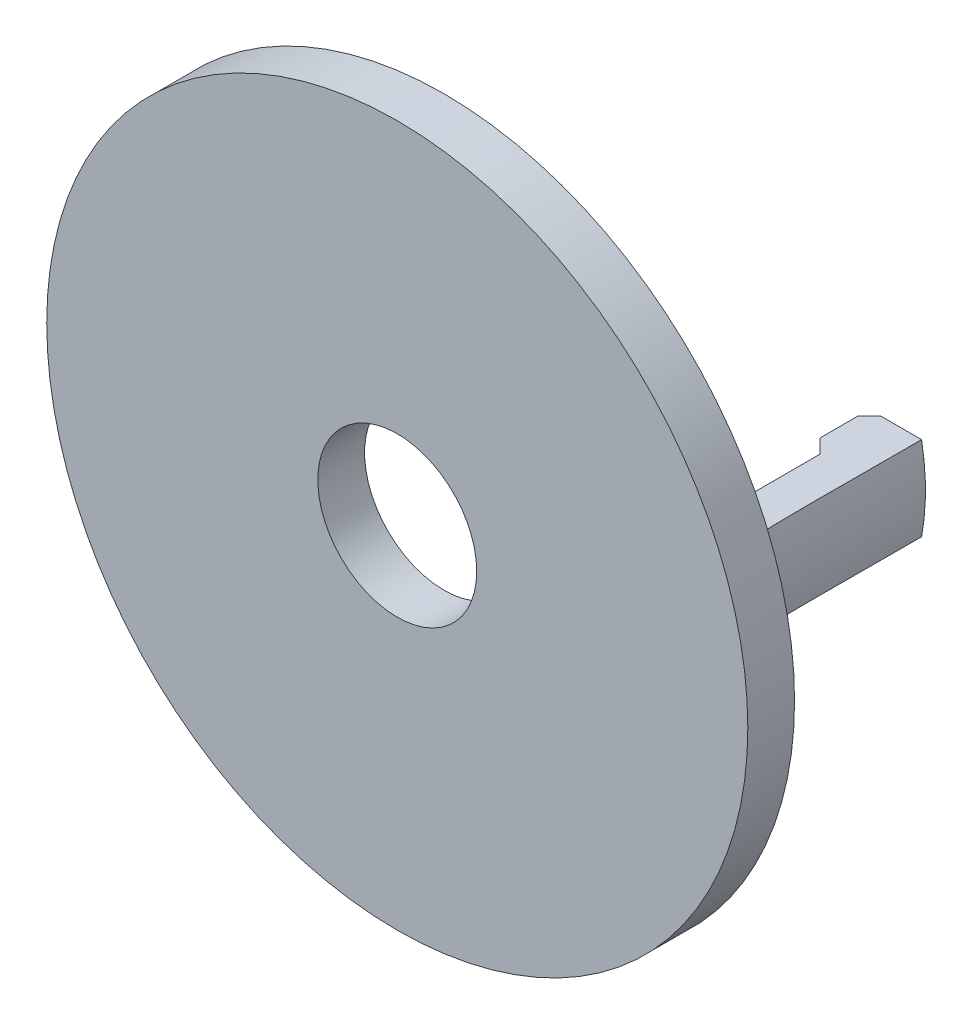
SolidWorks part; units mm, degrees
ref_plane "Front" through (0, 0, 0) normal (0, 0, 1) x (1, 0, 0)
ref_plane "Top" through (0, 0, 0) normal (0, 1, 0) x (1, 0, 0)
ref_plane "Right" through (0, 0, 0) normal (1, 0, 0) x (0, 0, -1)
sketch "Sketch1" plane through (0, 0, 0) normal (0, 0, 1) x (1, 0, 0)
  circle A0 centre (0, 0) radius 26.5
  circle A1 centre (0, 0) radius 37.5
  circle A2 centre (-2, 0) radius 26.5
  dimension "D1" = 53
  dimension "D2" = 75
  dimension "D3" = 2
sketch "Sketch4" plane through (0, 0, 0) normal (0, 0, 1) x (1, 0, 0)
  circle A0 centre (0, 0) radius 37.5
  dimension "D1" = 75
extrude "Boss-Extrude2" add sketch "Sketch4" along normal blind 5
sketch "Sketch5" plane through (0, 0, 5) normal (0, 0, 1) x (1, 0, 0)
  circle A0 centre (0, 0) radius 8.5
  dimension "D1" = 17
extrude "Cut-Extrude1" cut sketch "Sketch5" against normal through all
sketch "Sketch6" plane through (0, 0, 0) normal (0, 1, 0) x (1, 0, 0)
  line L0 (20, 0) -> (26.5, 0) construction
  line L1 (26.5, 0) -> (26.5, 27) construction
  line L2 (17.7071, 0) -> (26.5, 0)
  line L3 (26.5, 27) -> (20, 27) construction
  line L4 (20, 27) -> (18.5, 25.5) construction
  line L5 (18.5, 21) -> (20, 19.5) construction
  line L6 (20, 19.5) -> (20, 0) construction
  line L7 (20.5, 19.7071) -> (20.5, 2.7929)
  line L8 (20, 3) -> (17, 0) construction
  line L9 (20.5, 19.7071) -> (19, 21.2071)
  line L10 (18.5, 25.5) -> (18.5, 21) construction
  line L11 (19, 21.2071) -> (19, 25.2929)
  line L12 (26.5, 0) -> (26.5, 26.5)
  line L13 (17, 0) -> (20, 0) construction
  line L14 (20.5, 2.7929) -> (17.7071, 0)
  line L15 (19, 25.2929) -> (20.2071, 26.5)
  line L16 (20.2071, 26.5) -> (26.5, 26.5)
  line L17 (25, 26.5113) -> (25, 41.0721) construction
  line L18 (25, 12.4795) -> (25, 18.7128) construction
  spline S0 degree 3 poles (25, 26.5) (25, 22.4782) (24.9901, 20.5563) (25.0119, 14.9305) (24.7749, 4.9839) (26.5, 0) knots 0 0 0 0 0.446605 0.546605 1 1 1 1
  dimension "D1" = 135
  dimension "D2" = 6.5
  dimension "D3" = 8
  dimension "D4" = 27
  dimension "D5" = 7.5
  dimension "D6" = 0.5
  dimension "D7" = 0.5
  dimension "D8" = 0.5
  dimension "D9" = 0.5
  dimension "D10" = 3
  dimension "D11" = 3
  dimension "D12" = 0.5
  dimension "D13" = 1.5
  dimension "D14" = 0.5
extrude "Boss-Extrude3" add sketch "Sketch6" along normal blind 4.5 and the other way blind 4.5 contours L16 L15 L11 L9 L7 L14 L2 | L12 L16 region at (22.5841, 0, -13.0971) region at (25.7988, 0, -14.8725)
extrude "Cut-Extrude2" cut sketch "Sketch1" against normal through all contours A1 A2 A0 region at (-36.4393, 0, 0)
ref_axis "Axis1" through (0, 0, 0) along (0, 0, -1)
revolve "Cut-Revolve1" cut sketch "Sketch6<4>" angle 360 about axis through (0, 0, 0) along (0, 0, -1) region at (25.7988, 0, -14.8725)
sketch "Sketch6<4>" plane through (0, 0, 0) normal (0, 1, 0) x (1, 0, 0) same geometry as "Sketch6"
mirror "Mirror1" about plane through (0, 0, 0) normal (1, 0, 0) of "Boss-Extrude3", "Cut-Extrude2", "Cut-Revolve1"
equation "\"female_make_room\"=0.5"
equation "\"D6@Sketch6\"=\"female_make_room\""
equation "\"D8@Sketch6\"=\"female_make_room\""
equation "\"D7@Sketch6\"=\"female_make_room\""
equation "\"D9@Sketch6\"=\"female_make_room\""
equation "\"D12@Sketch6\"=\"female_make_room\""
equation "\"D14@Sketch6\"=\"female_make_room\""
